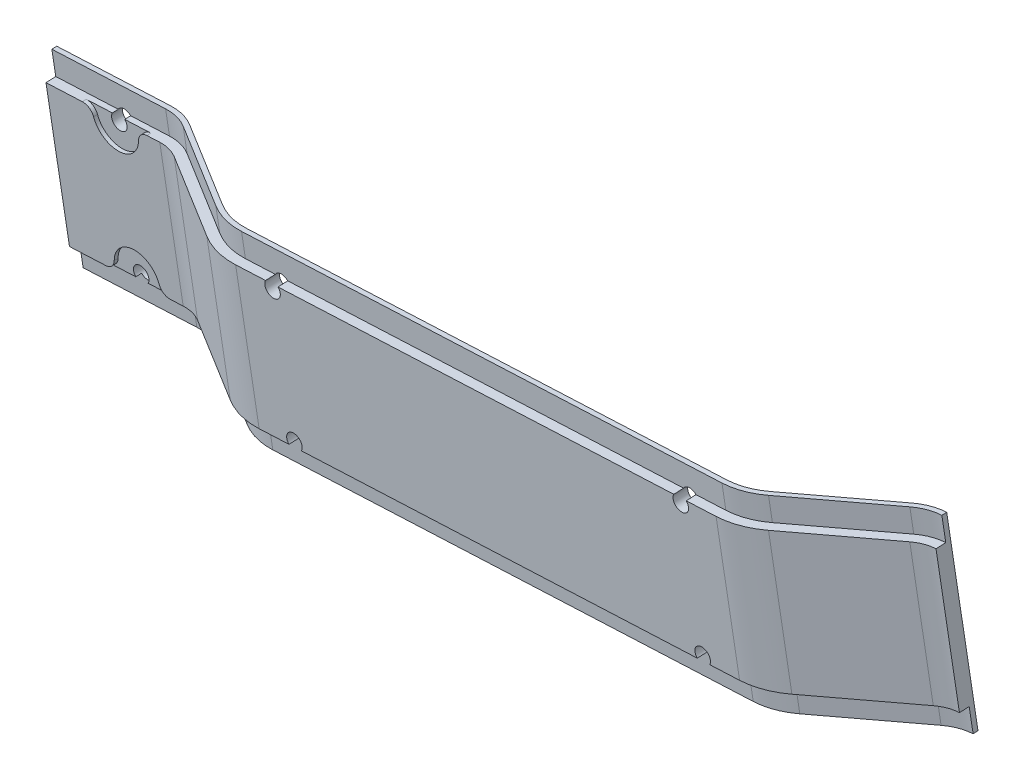
SolidWorks part; units mm, degrees
material "ABS"
ref_plane "前视基准面" through (0, 0, 0) normal (0, 0, 1) x (1, 0, 0)
ref_plane "上视基准面" through (0, 0, 0) normal (0, 1, 0) x (1, 0, 0)
ref_plane "右视基准面" through (0, 0, 0) normal (1, 0, 0) x (0, 0, -1)
other "Configuration Table"
sketch "草图2" plane through (-35.9528, 399.7424, 30.5662) normal (-0.0893, 0.9931, 0.0759) x (0.996, 0.0891, 0.0068)
  line L0 (491.2635, -1135.8026) -> (472.3863, -1123.9958) construction
  line L1 (464.962, -1121.7226) -> (358.5246, -1117.9612) construction
  line L2 (350.9583, -1119.7047) -> (331.2948, -1130.1494) construction
  line L3 (325.2417, -1131.5442) -> (302.5393, -1130.7419) construction
  line L4 (491.2635, -1135.8026) -> (472.3863, -1123.9958)
  line L5 (464.962, -1121.7226) -> (358.5246, -1117.9612)
  line L6 (350.9583, -1119.7047) -> (331.2948, -1130.1494)
  line L7 (325.2417, -1131.5442) -> (302.5393, -1130.7419)
  line L8 (492.8543, -1133.2591) -> (473.9771, -1121.4523)
  line L9 (465.0679, -1118.7245) -> (358.6305, -1114.9631)
  line L10 (349.551, -1117.0552) -> (329.8875, -1127.5)
  line L11 (325.3477, -1128.5461) -> (302.6452, -1127.7438)
  line L12 (302.6452, -1127.7438) -> (302.5393, -1130.7419)
  line L13 (497.3089, -1134.623) -> (497.203, -1137.6212)
  arc A0 (491.2635, -1135.8026) -> (497.203, -1137.6212) centre (497.6268, -1125.6286) ccw construction
  arc A1 (472.3863, -1123.9958) -> (464.962, -1121.7226) centre (464.4322, -1136.7132) ccw construction
  arc A2 (358.5246, -1117.9612) -> (350.9583, -1119.7047) centre (357.9948, -1132.9518) ccw construction
  arc A3 (325.2417, -1131.5442) -> (331.2948, -1130.1494) centre (325.6655, -1119.5517) ccw construction
  arc A4 (491.2635, -1135.8026) -> (497.203, -1137.6212) centre (497.6268, -1125.6286) ccw
  arc A5 (472.3863, -1123.9958) -> (464.962, -1121.7226) centre (464.4322, -1136.7132) ccw
  arc A6 (358.5246, -1117.9612) -> (350.9583, -1119.7047) centre (357.9948, -1132.9518) ccw
  arc A7 (325.2417, -1131.5442) -> (331.2948, -1130.1494) centre (325.6655, -1119.5517) ccw
  arc A8 (492.8543, -1133.2591) -> (497.3089, -1134.623) centre (497.6268, -1125.6286) ccw
  arc A9 (473.9771, -1121.4523) -> (465.0679, -1118.7245) centre (464.4322, -1136.7132) ccw
  arc A10 (358.6305, -1114.9631) -> (349.551, -1117.0552) centre (357.9948, -1132.9518) ccw
  arc A11 (325.3477, -1128.5461) -> (329.8875, -1127.5) centre (325.6655, -1119.5517) ccw
  dimension "D1" = 3
extrude "凸台-拉伸1" add sketch "草图2" against normal up to surface (40 mm away)
sketch "草图3" plane through (-35.9528, 399.7424, 30.5662) normal (-0.0893, 0.9931, 0.0759) x (0.996, 0.0891, 0.0068)
  line L4 (492.8543, -1133.2591) -> (473.9771, -1121.4523) construction
  line L5 (465.0679, -1118.7245) -> (358.6305, -1114.9631) construction
  line L6 (349.551, -1117.0552) -> (329.8875, -1127.5) construction
  line L7 (325.3477, -1128.5461) -> (302.6452, -1127.7438) construction
  line L8 (472.9166, -1123.148) -> (491.7938, -1134.9547)
  line L9 (358.5599, -1116.9618) -> (464.9973, -1120.7232)
  line L10 (330.8257, -1129.2663) -> (350.4892, -1118.8215)
  line L11 (302.5746, -1129.7426) -> (325.2771, -1130.5448)
  line L12 (472.9166, -1123.148) -> (491.7938, -1134.9547)
  line L13 (358.5599, -1116.9618) -> (464.9973, -1120.7232)
  line L14 (330.8257, -1129.2663) -> (350.4892, -1118.8215)
  line L15 (302.5746, -1129.7426) -> (325.2771, -1130.5448)
  line L16 (492.8543, -1133.2591) -> (473.9771, -1121.4523)
  line L17 (465.0679, -1118.7245) -> (358.6305, -1114.9631)
  line L18 (349.551, -1117.0552) -> (329.8875, -1127.5)
  line L19 (325.3477, -1128.5461) -> (302.6452, -1127.7438)
  line L20 (302.6452, -1127.7438) -> (302.5746, -1129.7426)
  line L21 (497.3089, -1134.623) -> (497.2383, -1136.6218)
  arc A4 (492.8543, -1133.2591) -> (497.3089, -1134.623) centre (497.6268, -1125.6286) ccw construction
  arc A5 (473.9771, -1121.4523) -> (465.0679, -1118.7245) centre (464.4322, -1136.7132) ccw construction
  arc A6 (358.6305, -1114.9631) -> (349.551, -1117.0552) centre (357.9948, -1132.9518) ccw construction
  arc A7 (325.3477, -1128.5461) -> (329.8875, -1127.5) centre (325.6655, -1119.5517) ccw construction
  arc A8 (491.7938, -1134.9547) -> (497.2383, -1136.6218) centre (497.6268, -1125.6286) ccw
  arc A9 (472.9166, -1123.148) -> (464.9973, -1120.7232) centre (464.4322, -1136.7132) ccw
  arc A10 (358.5599, -1116.9618) -> (350.4892, -1118.8215) centre (357.9948, -1132.9518) ccw
  arc A11 (325.2771, -1130.5448) -> (330.8257, -1129.2663) centre (325.6655, -1119.5517) ccw
  arc A12 (491.7938, -1134.9547) -> (497.2383, -1136.6218) centre (497.6268, -1125.6286) ccw
  arc A13 (472.9166, -1123.148) -> (464.9973, -1120.7232) centre (464.4322, -1136.7132) ccw
  arc A14 (358.5599, -1116.9618) -> (350.4892, -1118.8215) centre (357.9948, -1132.9518) ccw
  arc A15 (325.2771, -1130.5448) -> (330.8257, -1129.2663) centre (325.6655, -1119.5517) ccw
  arc A16 (492.8543, -1133.2591) -> (497.3089, -1134.623) centre (497.6268, -1125.6286) ccw
  arc A17 (473.9771, -1121.4523) -> (465.0679, -1118.7245) centre (464.4322, -1136.7132) ccw
  arc A18 (358.6305, -1114.9631) -> (349.551, -1117.0552) centre (357.9948, -1132.9518) ccw
  arc A19 (325.3477, -1128.5461) -> (329.8875, -1127.5) centre (325.6655, -1119.5517) ccw
  dimension "D1" = 1
extrude "切除-拉伸1" cut sketch "草图3" against normal blind 5
sketch "草图5" plane through (-38.7497, -87.401, 1097.4452) normal (0.0352, 0.0793, -0.9962) x (-0.9994, 0.0028, -0.0351)
  circle A0 centre (-458.8628, 439.2871) radius 1.6 construction
  circle A1 centre (-368.7211, 431.1983) radius 1.6 construction
  circle A2 centre (-458.8628, 439.2871) radius 1.6 construction
  circle A3 centre (-368.7211, 431.1983) radius 1.6 construction
  circle A4 centre (-458.8628, 439.2871) radius 1.7
  circle A5 centre (-368.7211, 431.1983) radius 1.7
  dimension "D1" = 3.4
  dimension "D2" = 3.4
extrude "切除-拉伸2" cut sketch "草图5" against normal blind 10
sketch "草图6" plane through (-39.3741, -88.8093, 1115.1282) normal (-0.0352, -0.0793, 0.9962) x (0.9994, -0.0028, 0.0351)
  circle A0 centre (318.142, 426.6596) radius 1.6 construction
  circle A1 centre (318.142, 426.6596) radius 1.6 construction
  circle A2 centre (318.142, 426.6596) radius 1.7
  dimension "D1" = 3.4
extrude "切除-拉伸3" cut sketch "草图6" against normal blind 55
sketch "草图7" plane through (-39.2686, -88.5713, 1112.1395) normal (0.0352, 0.0793, -0.9962) x (-0.9994, 0.0028, -0.0351)
  line L0 (-323.1718, 427.111) -> (-323.0824, 428.107)
  line L1 (-319.4219, 427.7785) -> (-328.0126, 428.5494) construction
  line L2 (-323.0824, 428.107) -> (-313.0228, 427.2043)
  line L3 (-305.3869, 426.5191) -> (-316.6833, 427.5328) construction
  line L4 (-313.0228, 427.2043) -> (-313.1122, 426.2083)
  arc A0 (-323.1718, 427.111) -> (-313.1122, 426.2083) centre (-318.142, 426.6596) ccw
  dimension "D1" = 10.1
  dimension "D2" = 90
extrude "切除-拉伸4" cut sketch "草图7" against normal blind 0.8
ref_plane "基准面2" through (-34.1664, 379.8803, 29.0475) normal (-0.0893, 0.9931, 0.0759) x (0.996, 0.0891, 0.0068)
mirror "镜向2" about plane through (-34.1664, 379.8803, 29.0475) normal (-0.0893, 0.9931, 0.0759) of "切除-拉伸4", "切除-拉伸3", "切除-拉伸2", "切除-拉伸1"
sketch "草图8" plane through (340.7041, 29.5431, 14.3828) normal (-0.9954, -0.0863, -0.042) x (-0.0419, -0.0036, 0.9991)
  line L8 (1141.0558, 281.6073) -> (1143.05, 281.4553)
  line L9 (1143.05, 281.4553) -> (1142.6699, 276.4697)
  line L10 (1142.6699, 276.4697) -> (1143.6671, 276.3937)
  line L11 (1143.6671, 276.3937) -> (1146.7072, 316.278)
  line L12 (1146.7072, 316.278) -> (1145.7101, 316.354)
  line L13 (1145.7101, 316.354) -> (1145.3301, 311.3685)
  line L14 (1145.3301, 311.3685) -> (1143.3359, 311.5205)
  line L15 (1143.3359, 311.5205) -> (1141.0558, 281.6073)
  line L16 (1141.0558, 281.6073) -> (1143.05, 281.4553)
  line L17 (1143.05, 281.4553) -> (1142.6699, 276.4697)
  line L18 (1142.6699, 276.4697) -> (1143.6671, 276.3937)
  line L19 (1143.6671, 276.3937) -> (1146.7072, 316.278)
  line L20 (1146.7072, 316.278) -> (1145.7101, 316.354)
  line L21 (1145.7101, 316.354) -> (1145.3301, 311.3685)
  line L22 (1145.3301, 311.3685) -> (1143.3359, 311.5205)
  line L23 (1143.3359, 311.5205) -> (1141.0558, 281.6073)
  dimension "D1" = 0
extrude "凸台-拉伸2" add sketch "草图8" along normal blind 2.5
sketch "草图9" plane through (-38.8552, -87.6391, 1100.4339) normal (-0.0352, -0.0793, 0.9962) x (0.9994, -0.0028, 0.0351)
  line L360 (435.8978, 429.2946) -> (446.5285, 414.1843)
  line L361 (449.976, 412.586) -> (452.2762, 412.7924)
  line L362 (455.0445, 418.7637) -> (444.4138, 433.8741)
  line L363 (440.9663, 435.4723) -> (438.6661, 435.2659)
  line L364 (435.7343, 429.1795) -> (446.3649, 414.0692)
  line L365 (440.9484, 435.6715) -> (438.6483, 435.4651)
  line L366 (455.208, 418.8788) -> (444.5774, 433.9891)
  line L367 (449.9939, 412.3868) -> (452.294, 412.5932)
  line L368 (435.7343, 429.1795) -> (446.3649, 414.0692) construction
  line L369 (440.9484, 435.6715) -> (438.6483, 435.4651) construction
  line L370 (455.208, 418.8788) -> (444.5774, 433.9891) construction
  line L371 (449.9939, 412.3868) -> (452.294, 412.5932) construction
  line L372 (415.449, 427.3593) -> (426.0796, 412.2489)
  line L373 (420.6631, 433.8513) -> (418.363, 433.6449)
  line L374 (434.9227, 417.0585) -> (424.2921, 432.1689)
  line L375 (429.7086, 410.5665) -> (432.0088, 410.7729)
  line L376 (415.449, 427.3593) -> (426.0796, 412.2489) construction
  line L377 (420.6631, 433.8513) -> (418.363, 433.6449) construction
  line L378 (434.9227, 417.0585) -> (424.2921, 432.1689) construction
  line L379 (429.7086, 410.5665) -> (432.0088, 410.7729) construction
  line L380 (395.1637, 425.539) -> (405.7943, 410.4286)
  line L381 (400.3778, 432.031) -> (398.0777, 431.8246)
  line L382 (414.6374, 415.2382) -> (404.0068, 430.3486)
  line L383 (409.4233, 408.7462) -> (411.7235, 408.9526)
  line L384 (395.1637, 425.539) -> (405.7943, 410.4286) construction
  line L385 (400.3778, 432.031) -> (398.0777, 431.8246) construction
  line L386 (414.6374, 415.2382) -> (404.0068, 430.3486) construction
  line L387 (409.4233, 408.7462) -> (411.7235, 408.9526) construction
  line L388 (374.8784, 423.7187) -> (385.509, 408.6083)
  line L389 (380.0925, 430.2107) -> (377.7924, 430.0043)
  line L390 (394.3521, 413.4179) -> (383.7215, 428.5283)
  line L391 (389.138, 406.9259) -> (391.4382, 407.1323)
  line L392 (374.8784, 423.7187) -> (385.509, 408.6083) construction
  line L393 (380.0925, 430.2107) -> (377.7924, 430.0043) construction
  line L394 (394.3521, 413.4179) -> (383.7215, 428.5283) construction
  line L395 (389.138, 406.9259) -> (391.4382, 407.1323) construction
  line L396 (415.6125, 427.4743) -> (426.2432, 412.364)
  line L397 (429.6907, 410.7657) -> (431.9909, 410.9721)
  line L398 (434.7592, 416.9434) -> (424.1285, 432.0538)
  line L399 (420.681, 433.6521) -> (418.3808, 433.4457)
  line L400 (395.3272, 425.6541) -> (405.9579, 410.5437)
  line L401 (409.4054, 408.9454) -> (411.7056, 409.1518)
  line L402 (414.4739, 415.1231) -> (403.8432, 430.2335)
  line L403 (400.3957, 431.8318) -> (398.0955, 431.6254)
  line L404 (375.0419, 423.8338) -> (385.6726, 408.7234)
  line L405 (389.1201, 407.1251) -> (391.4203, 407.3315)
  line L406 (394.1886, 413.3029) -> (383.5579, 428.4132)
  line L407 (380.1104, 430.0115) -> (377.8102, 429.8051)
  arc A364 (446.5285, 414.1843) -> (449.976, 412.586) centre (449.6364, 416.3708) ccw
  arc A365 (452.2762, 412.7924) -> (455.0445, 418.7637) centre (451.9365, 416.5772) ccw
  arc A366 (444.4138, 433.8741) -> (440.9663, 435.4723) centre (441.3059, 431.6875) ccw
  arc A367 (438.6661, 435.2659) -> (435.8978, 429.2946) centre (439.0058, 431.4811) ccw
  arc A368 (438.6483, 435.4651) -> (435.7343, 429.1795) centre (439.0058, 431.4811) ccw
  arc A369 (444.5774, 433.9891) -> (440.9484, 435.6715) centre (441.3059, 431.6875) ccw
  arc A370 (452.294, 412.5932) -> (455.208, 418.8788) centre (451.9365, 416.5772) ccw
  arc A371 (446.3649, 414.0692) -> (449.9939, 412.3868) centre (449.6364, 416.3708) ccw
  arc A372 (438.6483, 435.4651) -> (435.7343, 429.1795) centre (439.0058, 431.4811) ccw construction
  arc A373 (444.5774, 433.9891) -> (440.9484, 435.6715) centre (441.3059, 431.6875) ccw construction
  arc A374 (452.294, 412.5932) -> (455.208, 418.8788) centre (451.9365, 416.5772) ccw construction
  arc A375 (446.3649, 414.0692) -> (449.9939, 412.3868) centre (449.6364, 416.3708) ccw construction
  arc A376 (418.363, 433.6449) -> (415.449, 427.3593) centre (418.7205, 429.6609) ccw
  arc A377 (424.2921, 432.1689) -> (420.6631, 433.8513) centre (421.0206, 429.8673) ccw
  arc A378 (432.0088, 410.7729) -> (434.9227, 417.0585) centre (431.6513, 414.7569) ccw
  arc A379 (426.0796, 412.2489) -> (429.7086, 410.5665) centre (429.3511, 414.5505) ccw
  arc A380 (418.363, 433.6449) -> (415.449, 427.3593) centre (418.7205, 429.6609) ccw construction
  arc A381 (424.2921, 432.1689) -> (420.6631, 433.8513) centre (421.0206, 429.8673) ccw construction
  arc A382 (432.0088, 410.7729) -> (434.9227, 417.0585) centre (431.6513, 414.7569) ccw construction
  arc A383 (426.0796, 412.2489) -> (429.7086, 410.5665) centre (429.3511, 414.5505) ccw construction
  arc A384 (398.0777, 431.8246) -> (395.1637, 425.539) centre (398.4352, 427.8406) ccw
  arc A385 (404.0068, 430.3486) -> (400.3778, 432.031) centre (400.7353, 428.047) ccw
  arc A386 (411.7235, 408.9526) -> (414.6374, 415.2382) centre (411.366, 412.9366) ccw
  arc A387 (405.7943, 410.4286) -> (409.4233, 408.7462) centre (409.0658, 412.7302) ccw
  arc A388 (398.0777, 431.8246) -> (395.1637, 425.539) centre (398.4352, 427.8406) ccw construction
  arc A389 (404.0068, 430.3486) -> (400.3778, 432.031) centre (400.7353, 428.047) ccw construction
  arc A390 (411.7235, 408.9526) -> (414.6374, 415.2382) centre (411.366, 412.9366) ccw construction
  arc A391 (405.7943, 410.4286) -> (409.4233, 408.7462) centre (409.0658, 412.7302) ccw construction
  arc A392 (377.7924, 430.0043) -> (374.8784, 423.7187) centre (378.1499, 426.0203) ccw
  arc A393 (383.7215, 428.5283) -> (380.0925, 430.2107) centre (380.45, 426.2267) ccw
  arc A394 (391.4382, 407.1323) -> (394.3521, 413.4179) centre (391.0807, 411.1163) ccw
  arc A395 (385.509, 408.6083) -> (389.138, 406.9259) centre (388.7805, 410.9099) ccw
  arc A396 (377.7924, 430.0043) -> (374.8784, 423.7187) centre (378.1499, 426.0203) ccw construction
  arc A397 (383.7215, 428.5283) -> (380.0925, 430.2107) centre (380.45, 426.2267) ccw construction
  arc A398 (391.4382, 407.1323) -> (394.3521, 413.4179) centre (391.0807, 411.1163) ccw construction
  arc A399 (385.509, 408.6083) -> (389.138, 406.9259) centre (388.7805, 410.9099) ccw construction
  arc A400 (426.2432, 412.364) -> (429.6907, 410.7657) centre (429.3511, 414.5505) ccw
  arc A401 (431.9909, 410.9721) -> (434.7592, 416.9434) centre (431.6513, 414.7569) ccw
  arc A402 (424.1285, 432.0538) -> (420.681, 433.6521) centre (421.0206, 429.8673) ccw
  arc A403 (418.3808, 433.4457) -> (415.6125, 427.4743) centre (418.7205, 429.6609) ccw
  arc A404 (405.9579, 410.5437) -> (409.4054, 408.9454) centre (409.0658, 412.7302) ccw
  arc A405 (411.7056, 409.1518) -> (414.4739, 415.1231) centre (411.366, 412.9366) ccw
  arc A406 (403.8432, 430.2335) -> (400.3957, 431.8318) centre (400.7353, 428.047) ccw
  arc A407 (398.0955, 431.6254) -> (395.3272, 425.6541) centre (398.4352, 427.8406) ccw
  arc A408 (385.6726, 408.7234) -> (389.1201, 407.1251) centre (388.7805, 410.9099) ccw
  arc A409 (391.4203, 407.3315) -> (394.1886, 413.3029) centre (391.0807, 411.1163) ccw
  arc A410 (383.5579, 428.4132) -> (380.1104, 430.0115) centre (380.45, 426.2267) ccw
  arc A411 (377.8102, 429.8051) -> (375.0419, 423.8338) centre (378.1499, 426.0203) ccw
  dimension "D1" = 0
  dimension "D2" = 0
  dimension "D3" = 0
  dimension "D4" = 0
  dimension "D5" = 0.2
extrude "凸台-拉伸3" add sketch "草图9" along normal blind 2.5
mirror "镜向3" about plane through (448.3078, 121.8045, 1131.304) normal (0.0352, 0.0793, -0.9962) of "切除-拉伸3", "凸台-拉伸1", "切除-拉伸1", "切除-拉伸2", "切除-拉伸4", "镜向2", "凸台-拉伸2", "凸台-拉伸3"
sketch "草图10" plane through (-35.9528, 399.7424, 30.5662) normal (-0.0893, 0.9931, 0.0759) x (0.996, 0.0891, 0.0068)
  line L0 (358.6305, -1114.9631) -> (465.0679, -1118.7245) construction
  line L1 (281.9092, -1112.2518) -> (520.4481, -1120.6815)
  line L2 (281.9092, -1112.2518) -> (280.6845, -1146.9079)
  line L3 (280.6845, -1146.9079) -> (520.4481, -1155.3809)
  line L4 (520.4481, -1155.3809) -> (520.4481, -1120.6815)
extrude "切除-拉伸5" cut sketch "草图10" against normal mid plane 135
fillet "圆角1" radius 2.2 4 edges at (287.3453, 309.8614, 1125.3901) (277.2919, 308.9896, 1124.9657) (284.6657, 339.6545, 1127.6682) (274.6123, 338.7827, 1127.2438)
